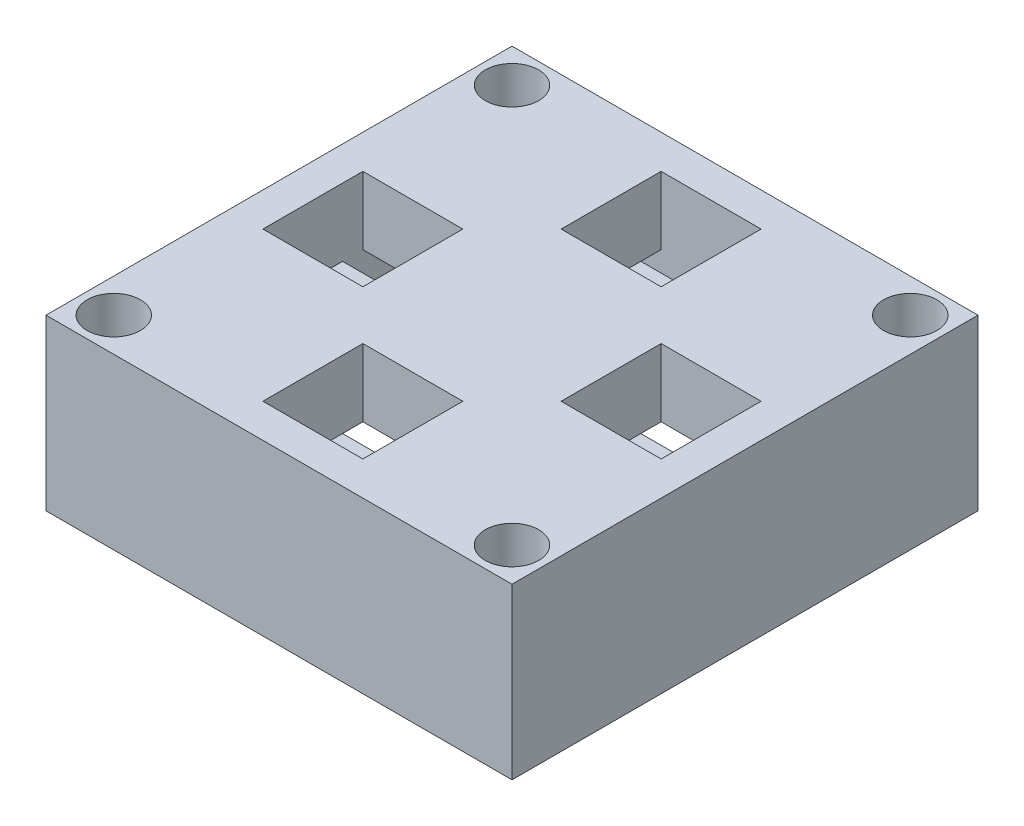
SolidWorks part; units mm, degrees
ref_plane "Front Plane" through (0, 0, 0) normal (0, 0, 1) x (1, 0, 0)
ref_plane "Top Plane" through (0, 0, 0) normal (0, 1, 0) x (1, 0, 0)
ref_plane "Right Plane" through (0, 0, 0) normal (1, 0, 0) x (0, 0, -1)
sketch "Sketch1" plane through (0, 0, 0) normal (0, 1, 0) x (1, 0, 0)
  line L1 (-27.5, 27.5) -> (27.5, 27.5)
  line L2 (-27.5, 27.5) -> (-27.5, -27.5)
  line L3 (-27.5, -27.5) -> (27.5, -27.5)
  line L4 (27.5, 27.5) -> (27.5, -27.5)
  line L5 (-27.5, 27.5) -> (27.5, -27.5) construction
  line L6 (-27.5, -27.5) -> (27.5, 27.5) construction
  line L7 (-5.9, 23.5) -> (5.9, 23.5)
  line L8 (-5.9, 23.5) -> (-5.9, 11.7)
  line L9 (-5.9, 11.7) -> (5.9, 11.7)
  line L10 (5.9, 23.5) -> (5.9, 11.7)
  line L11 (-5.9, 23.5) -> (5.9, 11.7) construction
  line L12 (-5.9, 11.7) -> (5.9, 23.5) construction
  line L13 (11.7, 5.9) -> (23.5, 5.9)
  line L14 (11.7, 5.9) -> (11.7, -5.9)
  line L15 (11.7, -5.9) -> (23.5, -5.9)
  line L16 (23.5, 5.9) -> (23.5, -5.9)
  line L17 (11.7, 5.9) -> (23.5, -5.9) construction
  line L18 (11.7, -5.9) -> (23.5, 5.9) construction
  line L19 (-23.5, 5.9) -> (-11.7, 5.9)
  line L20 (-23.5, 5.9) -> (-23.5, -5.9)
  line L21 (-23.5, -5.9) -> (-11.7, -5.9)
  line L22 (-11.7, 5.9) -> (-11.7, -5.9)
  line L23 (-23.5, 5.9) -> (-11.7, -5.9) construction
  line L24 (-23.5, -5.9) -> (-11.7, 5.9) construction
  line L25 (5.9, -23.5) -> (-5.9, -23.5)
  line L26 (5.9, -23.5) -> (5.9, -11.7)
  line L27 (5.9, -11.7) -> (-5.9, -11.7)
  line L28 (-5.9, -23.5) -> (-5.9, -11.7)
  line L29 (5.9, -23.5) -> (-5.9, -11.7) construction
  line L30 (5.9, -11.7) -> (-5.9, -23.5) construction
  point P0 (0, 0)
  point P6 (0, 17.6)
  point P11 (17.6, 0)
  point P16 (-17.6, 0)
  point P21 (0, -17.6)
  dimension "D1" = 55
  dimension "D2" = 55
  dimension "D3" = 11.8
  dimension "D4" = 11.8
  dimension "D5" = 11.8
  dimension "D6" = 11.8
  dimension "D7" = 11.8
  dimension "D8" = 11.8
  dimension "D9" = 11.8
  dimension "D10" = 11.8
  dimension "D11" = 4
  dimension "D12" = 4
  dimension "D13" = 4
  dimension "D14" = 4
  dimension "D15" = 27.5
  dimension "D16" = 27.5
  dimension "D17" = 27.5
extrude "Boss-Extrude1" add sketch "Sketch1" along normal blind 8
sketch "Sketch2" plane through (0, 0, 0) normal (0, -1, 0) x (1, 0, 0)
  line L0 (-5.9, 23.5) -> (-23.5, 23.5)
  line L1 (-11.8, 21.1) -> (11.8, 21.1)
  line L2 (-11.8, 21.1) -> (-11.8, 14.1)
  line L3 (-11.8, 14.1) -> (11.8, 14.1)
  line L4 (11.8, 21.1) -> (11.8, 14.1)
  line L5 (-11.8, 21.1) -> (11.8, 14.1) construction
  line L6 (-11.8, 14.1) -> (11.8, 21.1) construction
  line L12 (-23.5, 3.5) -> (23.5, 3.5)
  line L17 (-23.5, 3.5) -> (-23.5, -3.5)
  line L18 (-23.5, -3.5) -> (23.5, -3.5)
  line L19 (-11.8, -14.1) -> (11.8, -14.1)
  line L20 (-11.8, -14.1) -> (-11.8, -21.1)
  line L21 (-11.8, -21.1) -> (11.8, -21.1)
  line L22 (11.8, -14.1) -> (11.8, -21.1)
  line L23 (-11.8, -14.1) -> (11.8, -21.1) construction
  line L24 (-11.8, -21.1) -> (11.8, -14.1) construction
  line L25 (-23.5, -23.5) -> (-23.5, 23.5)
  line L26 (23.5, -23.5) -> (-23.5, -23.5)
  line L27 (-5.9, 23.5) -> (23.5, 23.5)
  line L28 (23.5, -23.5) -> (23.5, 23.5)
  line L31 (-5.9, 11.7) -> (-5.9, 23.5) construction
  line L32 (5.9, 11.7) -> (-5.9, 11.7) construction
  line L33 (-5.9, -23.5) -> (-5.9, -11.7) construction
  line L36 (23.5, 3.5) -> (23.5, -3.5)
  line L37 (-23.5, 3.5) -> (23.5, -3.5) construction
  line L38 (-23.5, -3.5) -> (23.5, 3.5) construction
  point P0 (0, 17.6)
  point P5 (-15.2275, 0.8547)
  point P6 (0, 0)
  point P10 (14.3332, 1.7102)
  point P15 (0, -17.6)
  point P40 (-5.9, -17.6)
  line M21 (-23.5, -5.9) -> (-23.5, 5.9)
  line M24 (5.9, -23.5) -> (-5.9, -23.5)
  line M27 (27.5, -27.5) -> (27.5, 27.5)
  line M28 (27.5, 27.5) -> (-27.5, 27.5)
  line M29 (-27.5, 27.5) -> (-27.5, -27.5)
  line M30 (-27.5, -27.5) -> (27.5, -27.5)
  line M31 (23.5, 5.9) -> (23.5, -5.9)
  line M36 (-5.9, 23.5) -> (5.9, 23.5)
  dimension "D1" = 23.6
  dimension "D2" = 7
  dimension "D1*(1/4)" = 5.8004
  dimension "D3" = 2.4
  dimension "D1/4" = 5.9
  dimension "D4" = 7
  dimension "D5" = 2.4
  dimension "D6" = 5.9
  dimension "D7" = 7
  dimension "D8" = 0
extrude "Boss-Extrude7" add sketch "Sketch2" along normal blind 12 contours L28 L26 L25 L0 L27 M30 M27 M28 M29 M24 M21 M36 M31 region at (0, 0, -26.7222)
extrude "Boss-Extrude8" add sketch "Sketch2<5>" along normal blind 8 contours L1 L4 L3 L2 | L12 L36 L18 L17 | L19 L22 L21 L20
sketch "Sketch2<5>" plane through (0, 0, 0) normal (0, -1, 0) x (1, 0, 0) same geometry as "Sketch2"
sketch "Sketch6" plane through (0, -12, 0) normal (0, -1, 0) x (1, 0, 0)
  circle A0 centre (-23.5, 23.5) radius 3.15
  circle A1 centre (23.5, 23.5) radius 3.15
  circle A2 centre (-23.5, -23.5) radius 3.15
  circle A3 centre (23.5, -23.5) radius 3.15
  point P14 (0, 0)
  dimension "D1" = 6.3
extrude "Cut-Extrude1" cut sketch "Sketch6" against normal through all
